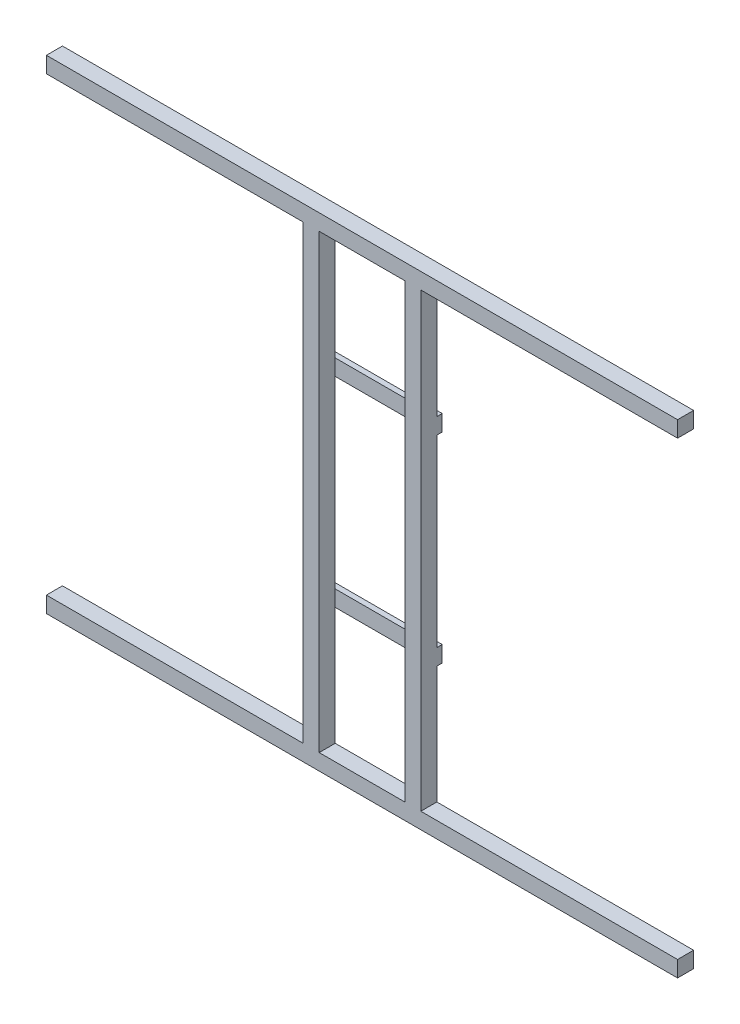
SolidWorks part; units mm, degrees
ref_plane "前视基准面" through (0, 0, 0) normal (0, 0, 1) x (1, 0, 0)
ref_plane "上视基准面" through (0, 0, 0) normal (0, 1, 0) x (1, 0, 0)
ref_plane "右视基准面" through (0, 0, 0) normal (1, 0, 0) x (0, 0, -1)
sketch "Sketch1" plane through (0, 0, 0) normal (0, 0, 1) x (1, 0, 0)
  line L0 (57, 0) -> (129.8959, 0) construction
  line L1 (57, 54.0142) -> (57, -54.0142) construction
  line L2 (85, 100.4999) -> (85, 76) construction
  line L3 (55, 100.9999) -> (-55, 100.9999)
  line L4 (55, 100.9999) -> (55, 85.9999)
  line L5 (55, 85.9999) -> (-55, 85.9999)
  line L6 (-55, 100.9999) -> (-55, 85.9999)
  line L7 (-85, 76) -> (-85, 100.4999) construction
  line L8 (-55, -100.9999) -> (-55, -85.9999)
  line L9 (55, -85.9999) -> (-55, -85.9999)
  line L10 (55, -100.9999) -> (55, -85.9999)
  line L11 (55, -100.9999) -> (-55, -100.9999)
  circle A0 centre (35, 93.4999) radius 2.1 construction
  dimension "D2" = 7.5
  dimension "D1" = 15
  dimension "D3" = 30
  dimension "D4" = 30
extrude "Extrude1" add sketch "Sketch1" along normal blind 5
sketch "Sketch2" plane through (0, 0, 5) normal (0, 0, 1) x (1, 0, 0)
  line L0 (55, -100.9999) -> (55, -85.9999) construction
  line L2 (55, -210.9999) -> (55, 210.9999)
  line L4 (40, -210.9999) -> (40, 210.9999)
  line L6 (-55, -210.9999) -> (-55, 210.9999)
  line L8 (-40, -210.9999) -> (-40, 210.9999)
  line L9 (-55, -85.9999) -> (-55, -100.9999) construction
  line L12 (-40, 210.9999) -> (40, 210.9999)
  line L13 (-295, -210.9999) -> (-55, -210.9999)
  line L14 (-295, -210.9999) -> (-295, -225.9999)
  line L15 (-295, -225.9999) -> (295, -225.9999)
  line L16 (295, -210.9999) -> (295, -225.9999)
  line L17 (-295, 210.9999) -> (-55, 210.9999)
  line L18 (-295, 210.9999) -> (-295, 225.9999)
  line L19 (-295, 225.9999) -> (295, 225.9999)
  line L20 (295, 210.9999) -> (295, 225.9999)
  line L21 (55, 210.9999) -> (295, 210.9999)
  line L22 (55, -210.9999) -> (295, -210.9999)
  line L23 (-40, -210.9999) -> (40, -210.9999)
  dimension "D1" = 15
  dimension "D2" = 15
  dimension "D5" = 590
  dimension "D6" = 240
  dimension "D7" = 15
  dimension "D8" = 15
extrude "Extrude2" add sketch "Sketch2" along normal blind 15
